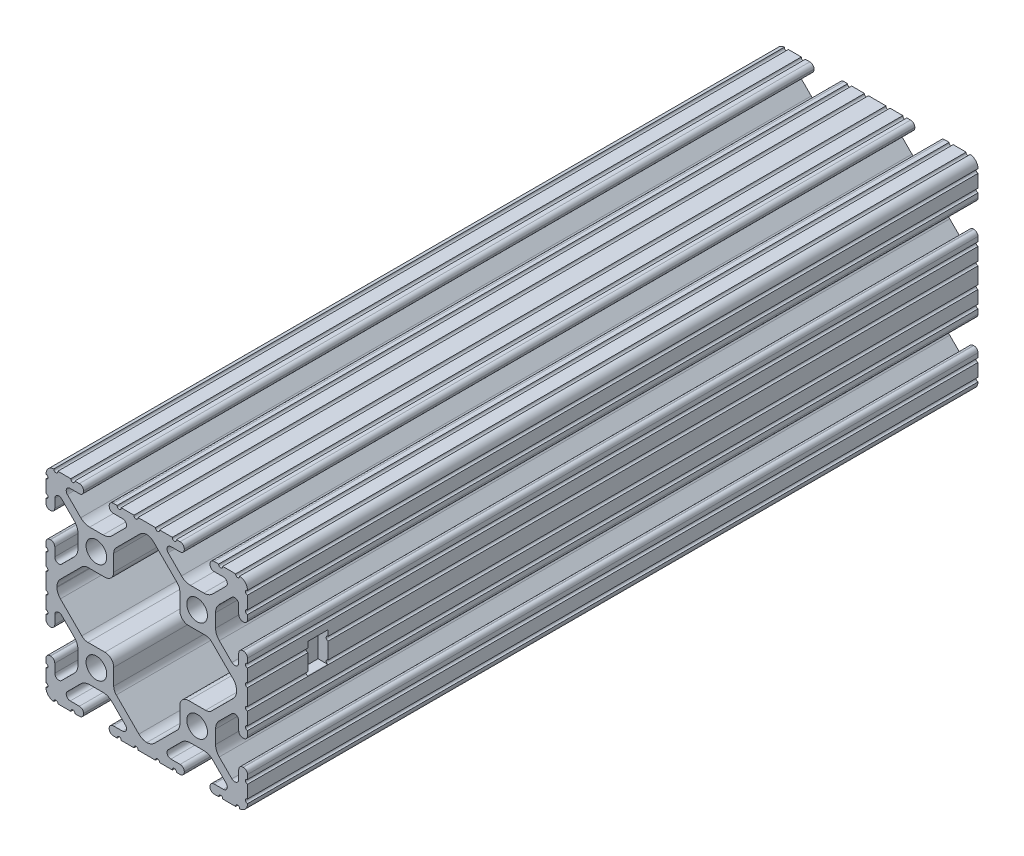
SolidWorks part; units mm, degrees
ref_plane "Front Plane" through (0, 0, 0) normal (0, 0, 1) x (1, 0, 0)
ref_plane "Top Plane" through (0, 0, 0) normal (0, 1, 0) x (1, 0, 0)
ref_plane "Right Plane" through (0, 0, 0) normal (1, 0, 0) x (0, 0, -1)
sketch "Sketch1" plane through (0, 0, 0) normal (0, 0, 1) x (1, 0, 0)
  line L0 (-7.684, -16.0797) -> (-1.9878, -21.7759)
  line L1 (-8.3312, -10.3886) -> (-8.3312, -14.5171)
  line L2 (-14.8165, -8.1788) -> (-10.541, -8.1788)
  line L3 (-21.7734, -2.1502) -> (-16.3772, -7.5334)
  line L4 (-22.6314, 0.0822) -> (-22.6314, -0.0822)
  line L5 (-16.3772, 7.5334) -> (-21.7734, 2.1502)
  line L6 (-10.541, 8.1788) -> (-14.8165, 8.1788)
  line L7 (-8.3312, 14.5171) -> (-8.3312, 10.3886)
  line L8 (-1.7956, 21.9681) -> (-7.684, 16.0797)
  line L9 (7.684, 16.0797) -> (1.7956, 21.9681)
  line L10 (8.3312, 10.389) -> (8.3312, 14.5171)
  line L11 (14.8161, 8.1792) -> (10.541, 8.1792)
  line L12 (21.7734, 2.1502) -> (16.3768, 7.5339)
  line L13 (22.6314, -0.0822) -> (22.6314, 0.0822)
  line L14 (16.3772, -7.5334) -> (21.7734, -2.1502)
  line L15 (10.541, -8.1788) -> (14.8165, -8.1788)
  line L16 (8.3312, -14.5171) -> (8.3312, -10.3886)
  line L17 (1.9878, -21.7759) -> (7.684, -16.0797)
  line L18 (7.4579, -25.4) -> (8.4051, -25.4)
  line L19 (9.4615, -24.3587) -> (9.4615, -24.2315)
  line L20 (8.4051, -23.1902) -> (6.0878, -23.1902)
  line L21 (5.388, -21.5008) -> (8.763, -18.1257)
  line L22 (11.0081, -17.1958) -> (14.3919, -17.1958)
  line L23 (16.637, -18.1257) -> (20.012, -21.5008)
  line L24 (19.2977, -23.1901) -> (16.9799, -23.1901)
  line L25 (15.9385, -24.2315) -> (15.9385, -24.3587)
  line L26 (16.9949, -25.4) -> (18.134, -25.4)
  line L27 (19.1384, -25.4) -> (22.4132, -25.4)
  line L28 (23.4176, -25.4) -> (23.4501, -25.4)
  line L29 (25.4, -23.2977) -> (25.4, -23.2686)
  line L30 (25.4, -22.2526) -> (25.4, -19.0252)
  line L31 (25.4, -18.0092) -> (25.4, -16.916)
  line L32 (24.3586, -15.8746) -> (24.2316, -15.8746)
  line L33 (23.1902, -16.916) -> (23.1902, -19.101)
  line L34 (21.4558, -19.8194) -> (18.2781, -16.6418)
  line L35 (17.3482, -14.3967) -> (17.3482, -11.0035)
  line L36 (18.2808, -8.7557) -> (21.4566, -5.5875)
  line L37 (23.1902, -6.3068) -> (23.1902, -8.484)
  line L38 (24.2316, -9.5254) -> (24.3586, -9.5254)
  line L39 (25.4, -8.484) -> (25.4, -7.3277)
  line L40 (25.4, -6.3117) -> (25.4, -3.0843)
  line L41 (25.4, -2.0683) -> (25.4, 2.0683)
  line L42 (25.4, 3.0843) -> (25.4, 6.3117)
  line L43 (25.4, 7.3277) -> (25.4, 8.484)
  line L44 (24.3586, 9.5254) -> (24.2316, 9.5254)
  line L45 (23.1902, 8.484) -> (23.1902, 6.3068)
  line L46 (21.4566, 5.5875) -> (18.2808, 8.7557)
  line L47 (17.3482, 11.0035) -> (17.3482, 14.3967)
  line L48 (18.2781, 16.6418) -> (21.4558, 19.8194)
  line L49 (23.1902, 19.101) -> (23.1902, 16.916)
  line L50 (24.2316, 15.8746) -> (24.3586, 15.8746)
  line L51 (25.4, 16.916) -> (25.4, 18.0092)
  line L52 (25.4, 19.0252) -> (25.4, 22.2526)
  line L53 (25.4, 23.2686) -> (25.4, 23.2977)
  line L54 (23.4501, 25.4) -> (23.4176, 25.4)
  line L55 (22.4132, 25.4) -> (19.1384, 25.4)
  line L56 (18.134, 25.4) -> (16.9949, 25.4)
  line L57 (15.9385, 24.3587) -> (15.9385, 24.2315)
  line L58 (16.9799, 23.1901) -> (19.2977, 23.1901)
  line L59 (20.012, 21.5008) -> (16.637, 18.1257)
  line L60 (14.3919, 17.1958) -> (11.0081, 17.1958)
  line L61 (8.763, 18.1257) -> (5.388, 21.5008)
  line L62 (6.0878, 23.1902) -> (8.4051, 23.1902)
  line L63 (9.4615, 24.2315) -> (9.4615, 24.3587)
  line L64 (8.4051, 25.4) -> (7.4579, 25.4)
  line L65 (6.4535, 25.4) -> (3.2145, 25.4)
  line L66 (2.2101, 25.4) -> (-2.2101, 25.4)
  line L67 (-3.2145, 25.4) -> (-6.4535, 25.4)
  line L68 (-7.4579, 25.4) -> (-8.4051, 25.4)
  line L69 (-9.4615, 24.3587) -> (-9.4615, 24.2315)
  line L70 (-8.4051, 23.1902) -> (-6.0878, 23.1902)
  line L71 (-5.388, 21.5008) -> (-8.763, 18.1257)
  line L72 (-11.0081, 17.1958) -> (-14.3919, 17.1958)
  line L73 (-16.637, 18.1257) -> (-20.012, 21.5008)
  line L74 (-19.2977, 23.1901) -> (-16.9799, 23.1901)
  line L75 (-15.9385, 24.2315) -> (-15.9385, 24.3587)
  line L76 (-16.9949, 25.4) -> (-18.134, 25.4)
  line L77 (-19.1384, 25.4) -> (-22.4132, 25.4)
  line L78 (-23.4176, 25.4) -> (-23.4501, 25.4)
  line L79 (-25.4, 23.2977) -> (-25.4, 23.2686)
  line L80 (-25.4, 22.2526) -> (-25.4, 19.0252)
  line L81 (-25.4, 18.0092) -> (-25.4, 16.916)
  line L82 (-24.3586, 15.8746) -> (-24.2316, 15.8746)
  line L83 (-23.1902, 16.916) -> (-23.1902, 19.101)
  line L84 (-21.4558, 19.8194) -> (-18.2781, 16.6418)
  line L85 (-17.3482, 14.3967) -> (-17.3482, 11.0035)
  line L86 (-18.2808, 8.7557) -> (-21.4566, 5.5875)
  line L87 (-23.1902, 6.3068) -> (-23.1902, 8.484)
  line L88 (-24.2316, 9.5254) -> (-24.3586, 9.5254)
  line L89 (-25.4, 8.484) -> (-25.4, 7.3277)
  line L90 (-25.4, 6.3117) -> (-25.4, 3.0843)
  line L91 (-25.4, 2.0683) -> (-25.4, -2.0683)
  line L92 (-25.4, -3.0843) -> (-25.4, -6.3117)
  line L93 (-25.4, -7.3277) -> (-25.4, -8.484)
  line L94 (-24.3586, -9.5254) -> (-24.2316, -9.5254)
  line L95 (-23.1902, -8.484) -> (-23.1902, -6.3068)
  line L96 (-21.4566, -5.5875) -> (-18.2808, -8.7557)
  line L97 (-17.3482, -11.0035) -> (-17.3482, -14.3967)
  line L98 (-18.2781, -16.6418) -> (-21.4558, -19.8194)
  line L99 (-23.1902, -19.101) -> (-23.1902, -16.916)
  line L100 (-24.2316, -15.8746) -> (-24.3586, -15.8746)
  line L101 (-25.4, -16.916) -> (-25.4, -18.0092)
  line L102 (-25.4, -19.0252) -> (-25.4, -22.2526)
  line L103 (-25.4, -23.2686) -> (-25.4, -23.2977)
  line L104 (-23.4501, -25.4) -> (-23.4176, -25.4)
  line L105 (-22.4132, -25.4) -> (-19.1384, -25.4)
  line L106 (-18.134, -25.4) -> (-16.9949, -25.4)
  line L107 (-15.9385, -24.3587) -> (-15.9385, -24.2315)
  line L108 (-16.9799, -23.1901) -> (-19.2977, -23.1901)
  line L109 (-20.012, -21.5008) -> (-16.637, -18.1257)
  line L110 (-14.3919, -17.1958) -> (-11.0081, -17.1958)
  line L111 (-8.763, -18.1257) -> (-5.388, -21.5008)
  line L112 (-6.0878, -23.1902) -> (-8.4051, -23.1902)
  line L113 (-9.4615, -24.2315) -> (-9.4615, -24.3587)
  line L114 (-8.4051, -25.4) -> (-7.4579, -25.4)
  line L115 (-6.4535, -25.4) -> (-3.2145, -25.4)
  line L116 (-2.2101, -25.4) -> (2.2101, -25.4)
  line L117 (3.2145, -25.4) -> (6.4535, -25.4)
  circle A0 centre (-12.7, 12.7) radius 2.6035
  circle A1 centre (12.7, 12.7) radius 2.6035
  circle A2 centre (12.7, -12.7) radius 2.6035
  circle A3 centre (-12.7, -12.7) radius 2.6035
  arc A4 (-1.9878, -21.7759) -> (0, -22.6304) centre (0.0777, -19.7104) ccw
  arc A5 (-8.3312, -14.5171) -> (-7.684, -16.0797) centre (-6.1214, -14.5171) ccw
  arc A6 (-8.3312, -10.3886) -> (-10.541, -8.1788) centre (-10.541, -10.3886) ccw
  arc A7 (-16.3772, -7.5334) -> (-14.8165, -8.1788) centre (-14.8165, -5.969) ccw
  arc A8 (-22.6314, -0.0822) -> (-21.7734, -2.1502) centre (-19.7104, -0.0822) ccw
  arc A9 (-21.7734, 2.1502) -> (-22.6314, 0.0822) centre (-19.7104, 0.0822) ccw
  arc A10 (-14.8165, 8.1788) -> (-16.3772, 7.5334) centre (-14.8165, 5.969) ccw
  arc A11 (-10.541, 8.1788) -> (-8.3312, 10.3886) centre (-10.541, 10.3886) ccw
  arc A12 (-7.684, 16.0797) -> (-8.3312, 14.5171) centre (-6.1214, 14.5171) ccw
  arc A13 (0, 22.8111) -> (-1.7956, 21.9681) centre (0.2699, 19.9026) ccw
  arc A14 (1.7956, 21.9681) -> (0, 22.8111) centre (-0.2699, 19.9026) ccw
  arc A15 (8.3312, 14.5171) -> (7.684, 16.0797) centre (6.1214, 14.5171) ccw
  arc A16 (8.3312, 10.389) -> (10.541, 8.1792) centre (10.541, 10.389) ccw
  arc A17 (16.3768, 7.5339) -> (14.8161, 8.1792) centre (14.8161, 5.9694) ccw
  arc A18 (22.6314, 0.0822) -> (21.7734, 2.1502) centre (19.7104, 0.0822) ccw
  arc A19 (21.7734, -2.1502) -> (22.6314, -0.0822) centre (19.7104, -0.0822) ccw
  arc A20 (14.8165, -8.1788) -> (16.3772, -7.5334) centre (14.8165, -5.969) ccw
  arc A21 (10.541, -8.1788) -> (8.3312, -10.3886) centre (10.541, -10.3886) ccw
  arc A22 (7.684, -16.0797) -> (8.3312, -14.5171) centre (6.1214, -14.5171) ccw
  arc A23 (0, -22.6304) -> (1.9878, -21.7759) centre (-0.0777, -19.7104) ccw
  arc A24 (7.4579, -25.4) -> (6.4535, -25.4) centre (6.9557, -25.3234) ccw
  arc A25 (8.4051, -25.4) -> (9.4615, -24.3587) centre (8.4201, -24.3587) ccw
  arc A26 (9.4615, -24.2315) -> (8.4051, -23.1902) centre (8.4201, -24.2315) ccw
  arc A27 (5.388, -21.5008) -> (6.0878, -23.1902) centre (6.0878, -22.2006) ccw
  arc A28 (11.0081, -17.1958) -> (8.763, -18.1257) centre (11.0081, -20.3708) ccw
  arc A29 (16.637, -18.1257) -> (14.3919, -17.1958) centre (14.3919, -20.3708) ccw
  arc A30 (19.2977, -23.1901) -> (20.012, -21.5008) centre (19.3122, -22.2006) ccw
  arc A31 (16.9799, -23.1901) -> (15.9385, -24.2315) centre (16.9799, -24.2315) ccw
  arc A32 (15.9385, -24.3587) -> (16.9949, -25.4) centre (16.9799, -24.3587) ccw
  arc A33 (19.1384, -25.4) -> (18.134, -25.4) centre (18.6362, -25.3234) ccw
  arc A34 (23.4176, -25.4) -> (22.4132, -25.4) centre (22.9154, -25.3234) ccw
  arc A35 (23.4501, -25.4) -> (25.4, -23.2977) centre (23.2918, -23.2977) ccw
  arc A36 (25.4, -22.2526) -> (25.4, -23.2686) centre (25.4, -22.7606) ccw
  arc A37 (25.4, -18.0092) -> (25.4, -19.0252) centre (25.4, -18.5172) ccw
  arc A38 (25.4, -16.916) -> (24.3586, -15.8746) centre (24.3586, -16.916) ccw
  arc A39 (24.2316, -15.8746) -> (23.1902, -16.916) centre (24.2316, -16.916) ccw
  arc A40 (21.4558, -19.8194) -> (23.1902, -19.101) centre (22.1742, -19.101) ccw
  arc A41 (17.3482, -14.3967) -> (18.2781, -16.6418) centre (20.5232, -14.3967) ccw
  arc A42 (18.2808, -8.7557) -> (17.3482, -11.0035) centre (20.5232, -11.0035) ccw
  arc A43 (23.1902, -6.3068) -> (21.4566, -5.5875) centre (22.1742, -6.3068) ccw
  arc A44 (23.1902, -8.484) -> (24.2316, -9.5254) centre (24.2316, -8.484) ccw
  arc A45 (24.3586, -9.5254) -> (25.4, -8.484) centre (24.3586, -8.484) ccw
  arc A46 (25.4, -6.3117) -> (25.4, -7.3277) centre (25.4, -6.8197) ccw
  arc A47 (25.4, -2.0683) -> (25.4, -3.0843) centre (25.4, -2.5763) ccw
  arc A48 (25.4, 3.0843) -> (25.4, 2.0683) centre (25.4, 2.5763) ccw
  arc A49 (25.4, 7.3277) -> (25.4, 6.3117) centre (25.4, 6.8197) ccw
  arc A50 (25.4, 8.484) -> (24.3586, 9.5254) centre (24.3586, 8.484) ccw
  arc A51 (24.2316, 9.5254) -> (23.1902, 8.484) centre (24.2316, 8.484) ccw
  arc A52 (21.4566, 5.5875) -> (23.1902, 6.3068) centre (22.1742, 6.3068) ccw
  arc A53 (17.3482, 11.0035) -> (18.2808, 8.7557) centre (20.5232, 11.0035) ccw
  arc A54 (18.2781, 16.6418) -> (17.3482, 14.3967) centre (20.5232, 14.3967) ccw
  arc A55 (23.1902, 19.101) -> (21.4558, 19.8194) centre (22.1742, 19.101) ccw
  arc A56 (23.1902, 16.916) -> (24.2316, 15.8746) centre (24.2316, 16.916) ccw
  arc A57 (24.3586, 15.8746) -> (25.4, 16.916) centre (24.3586, 16.916) ccw
  arc A58 (25.4, 19.0252) -> (25.4, 18.0092) centre (25.4, 18.5172) ccw
  arc A59 (25.4, 23.2686) -> (25.4, 22.2526) centre (25.4, 22.7606) ccw
  arc A60 (25.4, 23.2977) -> (23.4501, 25.4) centre (23.2918, 23.2977) ccw
  arc A61 (22.4132, 25.4) -> (23.4176, 25.4) centre (22.9154, 25.3234) ccw
  arc A62 (18.134, 25.4) -> (19.1384, 25.4) centre (18.6362, 25.3234) ccw
  arc A63 (16.9949, 25.4) -> (15.9385, 24.3587) centre (16.9799, 24.3587) ccw
  arc A64 (15.9385, 24.2315) -> (16.9799, 23.1901) centre (16.9799, 24.2315) ccw
  arc A65 (20.012, 21.5008) -> (19.2977, 23.1901) centre (19.3122, 22.2006) ccw
  arc A66 (14.3919, 17.1958) -> (16.637, 18.1257) centre (14.3919, 20.3708) ccw
  arc A67 (8.763, 18.1257) -> (11.0081, 17.1958) centre (11.0081, 20.3708) ccw
  arc A68 (6.0878, 23.1902) -> (5.388, 21.5008) centre (6.0878, 22.2006) ccw
  arc A69 (8.4051, 23.1902) -> (9.4615, 24.2315) centre (8.4201, 24.2315) ccw
  arc A70 (9.4615, 24.3587) -> (8.4051, 25.4) centre (8.4201, 24.3587) ccw
  arc A71 (6.4535, 25.4) -> (7.4579, 25.4) centre (6.9557, 25.3234) ccw
  arc A72 (2.2101, 25.4) -> (3.2145, 25.4) centre (2.7123, 25.3234) ccw
  arc A73 (-3.2145, 25.4) -> (-2.2101, 25.4) centre (-2.7123, 25.3234) ccw
  arc A74 (-7.4579, 25.4) -> (-6.4535, 25.4) centre (-6.9557, 25.3234) ccw
  arc A75 (-8.4051, 25.4) -> (-9.4615, 24.3587) centre (-8.4201, 24.3587) ccw
  arc A76 (-9.4615, 24.2315) -> (-8.4051, 23.1902) centre (-8.4201, 24.2315) ccw
  arc A77 (-5.388, 21.5008) -> (-6.0878, 23.1902) centre (-6.0878, 22.2006) ccw
  arc A78 (-11.0081, 17.1958) -> (-8.763, 18.1257) centre (-11.0081, 20.3708) ccw
  arc A79 (-16.637, 18.1257) -> (-14.3919, 17.1958) centre (-14.3919, 20.3708) ccw
  arc A80 (-19.2977, 23.1901) -> (-20.012, 21.5008) centre (-19.3122, 22.2006) ccw
  arc A81 (-16.9799, 23.1901) -> (-15.9385, 24.2315) centre (-16.9799, 24.2315) ccw
  arc A82 (-15.9385, 24.3587) -> (-16.9949, 25.4) centre (-16.9799, 24.3587) ccw
  arc A83 (-19.1384, 25.4) -> (-18.134, 25.4) centre (-18.6362, 25.3234) ccw
  arc A84 (-23.4176, 25.4) -> (-22.4132, 25.4) centre (-22.9154, 25.3234) ccw
  arc A85 (-23.4501, 25.4) -> (-25.4, 23.2977) centre (-23.2918, 23.2977) ccw
  arc A86 (-25.4, 22.2526) -> (-25.4, 23.2686) centre (-25.4, 22.7606) ccw
  arc A87 (-25.4, 18.0092) -> (-25.4, 19.0252) centre (-25.4, 18.5172) ccw
  arc A88 (-25.4, 16.916) -> (-24.3586, 15.8746) centre (-24.3586, 16.916) ccw
  arc A89 (-24.2316, 15.8746) -> (-23.1902, 16.916) centre (-24.2316, 16.916) ccw
  arc A90 (-21.4558, 19.8194) -> (-23.1902, 19.101) centre (-22.1742, 19.101) ccw
  arc A91 (-17.3482, 14.3967) -> (-18.2781, 16.6418) centre (-20.5232, 14.3967) ccw
  arc A92 (-18.2808, 8.7557) -> (-17.3482, 11.0035) centre (-20.5232, 11.0035) ccw
  arc A93 (-23.1902, 6.3068) -> (-21.4566, 5.5875) centre (-22.1742, 6.3068) ccw
  arc A94 (-23.1902, 8.484) -> (-24.2316, 9.5254) centre (-24.2316, 8.484) ccw
  arc A95 (-24.3586, 9.5254) -> (-25.4, 8.484) centre (-24.3586, 8.484) ccw
  arc A96 (-25.4, 6.3117) -> (-25.4, 7.3277) centre (-25.4, 6.8197) ccw
  arc A97 (-25.4, 2.0683) -> (-25.4, 3.0843) centre (-25.4, 2.5763) ccw
  arc A98 (-25.4, -3.0843) -> (-25.4, -2.0683) centre (-25.4, -2.5763) ccw
  arc A99 (-25.4, -7.3277) -> (-25.4, -6.3117) centre (-25.4, -6.8197) ccw
  arc A100 (-25.4, -8.484) -> (-24.3586, -9.5254) centre (-24.3586, -8.484) ccw
  arc A101 (-24.2316, -9.5254) -> (-23.1902, -8.484) centre (-24.2316, -8.484) ccw
  arc A102 (-21.4566, -5.5875) -> (-23.1902, -6.3068) centre (-22.1742, -6.3068) ccw
  arc A103 (-17.3482, -11.0035) -> (-18.2808, -8.7557) centre (-20.5232, -11.0035) ccw
  arc A104 (-18.2781, -16.6418) -> (-17.3482, -14.3967) centre (-20.5232, -14.3967) ccw
  arc A105 (-23.1902, -19.101) -> (-21.4558, -19.8194) centre (-22.1742, -19.101) ccw
  arc A106 (-23.1902, -16.916) -> (-24.2316, -15.8746) centre (-24.2316, -16.916) ccw
  arc A107 (-24.3586, -15.8746) -> (-25.4, -16.916) centre (-24.3586, -16.916) ccw
  arc A108 (-25.4, -19.0252) -> (-25.4, -18.0092) centre (-25.4, -18.5172) ccw
  arc A109 (-25.4, -23.2686) -> (-25.4, -22.2526) centre (-25.4, -22.7606) ccw
  arc A110 (-25.4, -23.2977) -> (-23.4501, -25.4) centre (-23.2918, -23.2977) ccw
  arc A111 (-22.4132, -25.4) -> (-23.4176, -25.4) centre (-22.9154, -25.3234) ccw
  arc A112 (-18.134, -25.4) -> (-19.1384, -25.4) centre (-18.6362, -25.3234) ccw
  arc A113 (-16.9949, -25.4) -> (-15.9385, -24.3587) centre (-16.9799, -24.3587) ccw
  arc A114 (-15.9385, -24.2315) -> (-16.9799, -23.1901) centre (-16.9799, -24.2315) ccw
  arc A115 (-20.012, -21.5008) -> (-19.2977, -23.1901) centre (-19.3122, -22.2006) ccw
  arc A116 (-14.3919, -17.1958) -> (-16.637, -18.1257) centre (-14.3919, -20.3708) ccw
  arc A117 (-8.763, -18.1257) -> (-11.0081, -17.1958) centre (-11.0081, -20.3708) ccw
  arc A118 (-6.0878, -23.1902) -> (-5.388, -21.5008) centre (-6.0878, -22.2006) ccw
  arc A119 (-8.4051, -23.1902) -> (-9.4615, -24.2315) centre (-8.4201, -24.2315) ccw
  arc A120 (-9.4615, -24.3587) -> (-8.4051, -25.4) centre (-8.4201, -24.3587) ccw
  arc A121 (-6.4535, -25.4) -> (-7.4579, -25.4) centre (-6.9557, -25.3234) ccw
  arc A122 (-2.2101, -25.4) -> (-3.2145, -25.4) centre (-2.7123, -25.3234) ccw
  arc A123 (3.2145, -25.4) -> (2.2101, -25.4) centre (2.7123, -25.3234) ccw
extrude "Boss-Extrude1" add sketch "Sketch1" along normal mid plane 184.15
sketch "Sketch3" plane through (-25.4, 0, 0) normal (-1, 0, 0) x (0, 0, 1)
  line L0 (41.275, -25.4) -> (79.375, 13.3708) construction
  line L3 (92.075, -25.4) -> (-92.075, -25.4) construction
  line L4 (79.375, 13.3708) -> (79.375, -25.4) construction
  line L5 (79.375, -25.4) -> (41.275, -25.4) construction
  line L7 (92.075, -19.0252) -> (92.075, -22.2526) construction
  line L8 (74.295, 4.5491) -> (74.295, 11.0035) construction
  line L9 (76.835, 4.5491) -> (71.755, 4.5491)
  line L10 (76.835, 4.5491) -> (76.835, -3.0709)
  line L11 (76.835, -3.0709) -> (71.755, -3.0709)
  line L12 (71.755, 4.5491) -> (71.755, -3.0709)
  line L13 (92.075, 11.0035) -> (-92.075, 11.0035) construction
  line L14 (74.295, -3.0709) -> (74.295, -9.5254) construction
  line L15 (92.075, -9.5254) -> (-92.075, -9.5254) construction
  point P11 (76.835, 0.7391)
  dimension "D1" = 38.1
  dimension "D2" = 45.5
  dimension "D3" = 50.8
  dimension "D4" = 7.62
  dimension "D5" = 2.54
  dimension "D6" = 5.08
extrude "Cut-Extrude3" cut sketch "Sketch3" against normal blind 2.54
extrude "Cut-Extrude4" cut sketch "Sketch3<2>" along normal blind 2.54 from surface starting at face at (25.4, 4.698, 0)
sketch "Sketch3<2>" plane through (-25.4, 0, 0) normal (-1, 0, 0) x (0, 0, 1) same geometry as "Sketch3"
